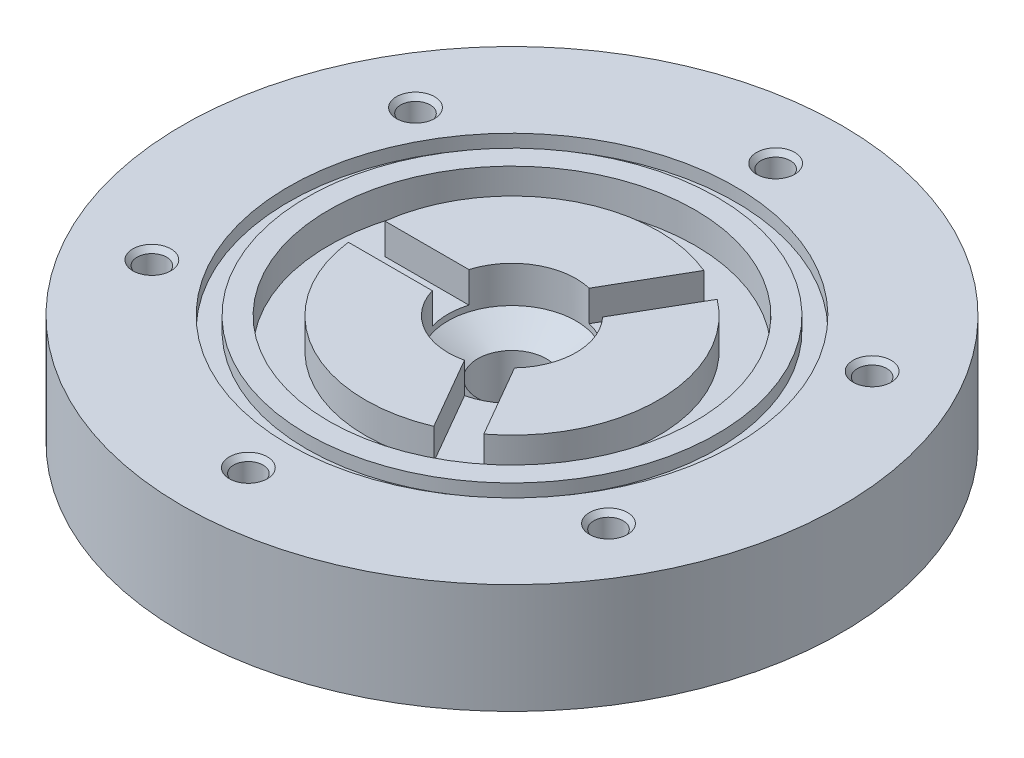
SolidWorks part; units mm, degrees
ref_plane "Front Plane" through (0, 0, 0) normal (0, 0, 1) x (1, 0, 0)
ref_plane "Top Plane" through (0, 0, 0) normal (0, 1, 0) x (1, 0, 0)
ref_plane "Right Plane" through (0, 0, 0) normal (1, 0, 0) x (0, 0, -1)
sketch "Sketch1" plane through (0, 0, 0) normal (0, 1, 0) x (1, 0, 0)
  circle A0 centre (0, 0) radius 57.15
  point P0 (0, 0)
  dimension "D3" = 114.3
extrude "Boss-Extrude1" add sketch "Sketch1" along normal blind 19.05
hole_wizard "7/8 (0.875) Diameter Hole1" positions "Sketch2" profile "Sketch3" hole size "7/8" standard "ANSI Inch"
sketch "Sketch2" plane through (0, 19.05, 0) normal (0, 1, 0) x (1, 0, 0)
  point P0 (0, 0)
sketch "Sketch3" plane through (0, 19.05, 0) normal (1, 0, 0) x (0, 0, 1)
  line L0 (0, 0) -> (0, 13.0271)
  line L1 (0, 13.0271) -> (11.1125, 6.35)
  line L2 (11.1125, 6.35) -> (11.1125, 0)
  line L5 (11.1125, 0) -> (0, 0)
  line L10 (0, 13.0271) -> (-11.1125, 6.35) construction
  line L11 (0, -6.35) -> (0, 107.95) construction
  dimension "Hole Dia." = 22.225
  dimension "Hole Depth" = 6.35
  dimension "Drill Angle" = 118
sketch "Sketch4" plane through (0, 19.05, 0) normal (0, 1, 0) x (1, 0, 0)
  circle A0 centre (0, 0) radius 5.9531
  dimension "D1" = 11.9062
extrude "Cut-Extrude1" cut sketch "Sketch4" against normal through all both and the other way through all
sketch "Annulus Channel" plane through (0, 19.05, 0) normal (0, 1, 0) x (1, 0, 0)
  line L0 (0, 0) -> (-57.15, 0) construction
  line L2 (-10.6493, 3.175) -> (-25.2008, 3.175)
  line L3 (-10.6493, -3.175) -> (-25.2008, -3.175)
  line L4 (0, -3.175) -> (-63.5, -3.175) construction
  line L5 (0, 3.175) -> (-63.5, 3.175) construction
  line L6 (2.575, 10.81) -> (9.8508, 23.412)
  line L7 (8.0743, 7.635) -> (15.35, 20.237)
  line L8 (0, 0) -> (28.575, 49.4934) construction
  line L9 (8.0743, -7.635) -> (15.35, -20.237)
  line L10 (2.575, -10.81) -> (9.8508, -23.412)
  line L11 (0, 0) -> (28.575, -49.4934) construction
  line L12 (0, 0) -> (-63.5, 0) construction
  arc A0 (15.35, -20.237) -> (15.35, 20.237) centre (0, 0) ccw
  circle A1 centre (0, 0) radius 31.75
  arc A2 (2.575, -10.81) -> (8.0743, -7.635) centre (0, 0) ccw
  arc A3 (-10.6493, 3.175) -> (-10.6493, -3.175) centre (0, 0) ccw
  arc A4 (8.0743, 7.635) -> (2.575, 10.81) centre (0, 0) ccw
  arc A5 (-25.2008, -3.175) -> (9.8508, -23.412) centre (0, 0) ccw
  arc A6 (9.8508, 23.412) -> (-25.2008, 3.175) centre (0, 0) ccw
  circle A8 centre (0, 0) radius 57.15 construction
  point P29 (0, 0)
  dimension "D1" = 50.8
  dimension "D2" = 63.5
  dimension "D5" = 22.225
  dimension "D7" = 6.35
  dimension "D3" = 3.175
  dimension "D4" = 3.175
  dimension "D6" = 3
ref_axis "Axis1" through (0, 12.7, 0) along (0, 1, 0)
extrude "Annulus Channel Depth" cut sketch "Annulus Channel" against normal blind 5.334
sketch "Sketch6" plane through (0, 19.05, 0) normal (0, 1, 0) x (1, 0, 0)
  circle A0 centre (0, 0) radius 53.975 construction
  dimension "D1" = 107.95
sketch "Sketch7" plane through (0, 19.05, 0) normal (0, 1, 0) x (1, 0, 0)
  circle A0 centre (0, 0) radius 35.56
  circle A1 centre (0, 0) radius 38.735
  dimension "D1" = 71.12
  dimension "D2" = 77.47
extrude "Cut-Extrude5" cut sketch "Sketch7" against normal blind 2.286
hole_wizard "1/4-20 Tapped Hole1" positions "Sketch8" profile "Sketch9" tap size "1/4-20" standard "ANSI Inch"
sketch "Sketch8" plane through (0, 19.05, 0) normal (0, 1, 0) x (1, 0, 0)
  point P0 (0, 45.72)
  dimension "D1" = 45.72
sketch "Sketch9" plane through (0, 19.05, -45.72) normal (1, 0, 0) x (0, 0, 1)
  line L0 (0, 0) -> (0, 15.5038)
  line L1 (0, 15.5038) -> (2.5527, 13.97)
  line L2 (2.5527, 13.97) -> (2.5527, 0.862)
  line L3 (2.5527, 0.862) -> (3.302, 0)
  line L5 (3.302, 0) -> (0, 0)
  line L6 (-2.5527, 0.862) -> (-3.302, 0) construction
  line L10 (0, 15.5038) -> (-2.5527, 13.97) construction
  line L11 (0, -6.35) -> (0, 107.95) construction
  dimension "Tap Drill Dia." = 5.1054
  dimension "Tap Drill Depth" = 13.97
  dimension "Near C'Sink Dia." = 6.604
  dimension "Near C'Sink Angle" = 82
  dimension "Drill Angle" = 118
cosmetic thread "Hole Thread1" parameters "D1"=11.43, "D2"=6.35
pattern_circular "CirPattern1" count 6 over 360 about axis through (0, 12.7, 0) along (0, 1, 0) of "1/4-20 Tapped Hole1"
